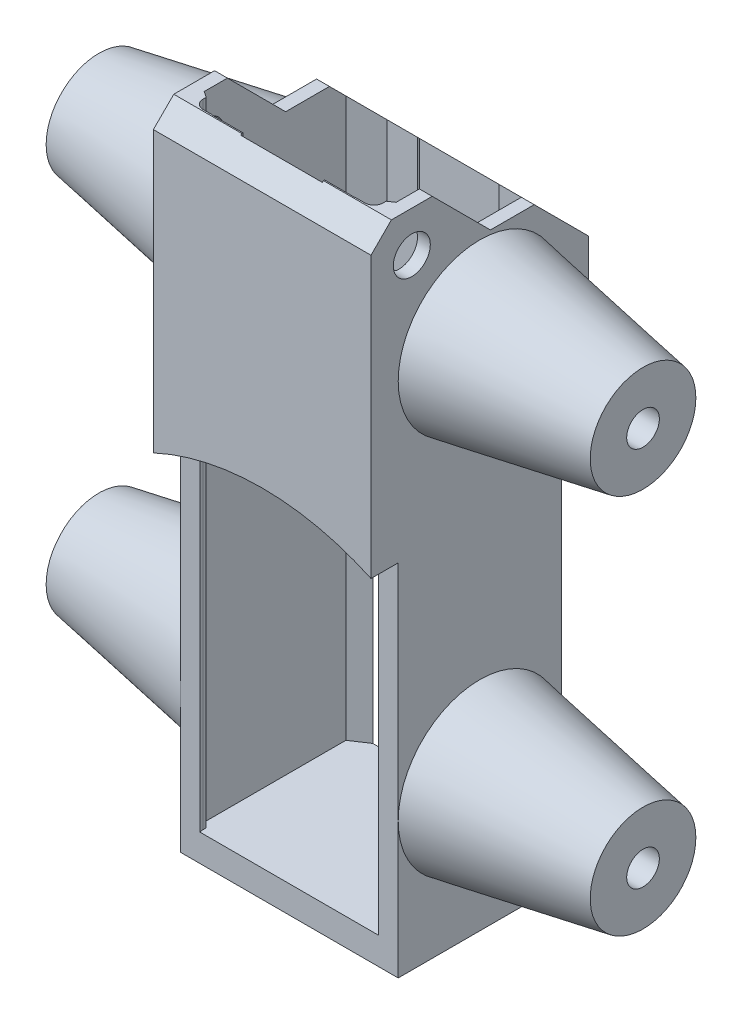
SolidWorks part; units mm, degrees
ref_plane "Front Plane" through (0, 0, 0) normal (0, 0, 1) x (1, 0, 0)
ref_plane "Top Plane" through (0, 0, 0) normal (0, 1, 0) x (1, 0, 0)
ref_plane "Right Plane" through (0, 0, 0) normal (1, 0, 0) x (0, 0, -1)
sketch "Sketch1" plane through (0, 0, 0) normal (0, 1, 0) x (1, 0, 0)
  line L0 (4.7625, -10.1854) -> (8.3298, -10.1854)
  line L5 (-4.7625, 10.1854) -> (-4.7625, 10.4394)
  line L6 (-12.7, -12.7) -> (12.7, -12.7)
  line L7 (4.7625, 10.1854) -> (8.3298, 10.1854)
  line L8 (-8.3298, 10.1854) -> (-11.2014, 8.271)
  line L9 (-8, 10.1) -> (-11, 8.1) construction
  line L10 (0, 0) -> (-11.2014, 0) construction
  line L11 (0, 0) -> (0, 10.4394) construction
  line L12 (-8.3298, -10.1854) -> (-8.3769, -10.154)
  line L13 (8.3298, -10.1854) -> (8.3769, -10.154)
  line L14 (8.3298, 10.1854) -> (11.2014, 8.271)
  line L15 (-8.3298, 10.1854) -> (-4.7625, 10.1854)
  line L16 (-12.7, 12.7) -> (-12.7, -12.7)
  line L17 (12.7, 12.7) -> (12.7, -12.7)
  line L34 (-10.504, -8.7359) -> (-11.2014, -8.271)
  line L35 (8.3769, -10.154) -> (9.4165, -10.154)
  line L36 (9.5863, -10.1409) -> (9.6154, -10.1409)
  line L37 (-9.5863, -10.1409) -> (-9.6154, -10.1409)
  line L38 (-8.75, -10.154) -> (-9.4165, -10.154)
  line L39 (-10.504, -9.1) -> (-10.504, -8.9)
  line L40 (-9.5863, -10.1409) -> (-9.6154, -10.1409)
  line L41 (-8.3769, -10.154) -> (-9.4165, -10.154)
  line L42 (-10.504, -9.1) -> (-10.504, -8.7359)
  line L43 (10.504, -9.1) -> (10.504, -8.7359)
  line L44 (10.504, -8.7359) -> (11.2014, -8.271)
  line L284 (-12.7, 12.7) -> (12.7, 12.7)
  line L286 (-12.7, -12.7) -> (12.7, 12.7) construction
  line L287 (-12.7, 12.7) -> (12.7, -12.7) construction
  line L288 (-8.3298, -10.1854) -> (-4.7625, -10.1854)
  line L289 (-11.2014, -8.271) -> (-11.2014, 8.271)
  line L291 (11.2014, -8.271) -> (11.2014, 8.271)
  line L326 (-4.7625, 10.4394) -> (4.7625, 10.4394)
  line L327 (4.7625, 10.4394) -> (4.7625, 10.1854)
  line L328 (-4.7625, -10.1854) -> (-4.7625, -10.4394)
  line L335 (-4.7625, -10.4394) -> (4.7625, -10.4394)
  line L338 (4.7625, -10.4394) -> (4.7625, -10.1854)
  arc A7 (9.5863, -10.1409) -> (9.4165, -10.154) centre (9.4168, -9.0458) cw
  arc A8 (-9.5863, -10.1409) -> (-9.4165, -10.154) centre (-9.4168, -9.0458) ccw
  arc A9 (-10.504, -9.1) -> (-9.6154, -10.1409) centre (-9.45, -9.1) ccw
  arc A10 (-9.5863, -10.1409) -> (-9.4165, -10.154) centre (-9.4168, -9.0458) ccw
  arc A11 (-10.504, -9.1) -> (-9.6154, -10.1409) centre (-9.45, -9.1) ccw
  arc A12 (10.504, -9.1) -> (9.6154, -10.1409) centre (9.45, -9.1) cw
  point P0 (0, 0)
  point P6 (0, 0)
  point P15 (0, 10.4394)
  point P23 (0, -10.4394)
  dimension "D1" = 25.4
  dimension "D2" = 25.4
  dimension "D3" = 0.254
  dimension "D5" = 9.525
  dimension "D6" = 22.4028
  dimension "D7" = 0.254
  dimension "D8" = 20.3708
  dimension "D9" = 0.254
  dimension "D15" = 0.254
extrude "Boss-Extrude1" add sketch "Sketch1" along normal blind 67.056
sketch "Sketch4" plane through (0, 0, 0) normal (0, -1, 0) x (-1, 0, 0)
  line L1 (12.7, -12.7) -> (-12.7, -12.7)
  line L2 (12.7, -12.7) -> (12.7, 12.7)
  line L3 (12.7, 12.7) -> (-12.7, 12.7)
  line L4 (-12.7, -12.7) -> (-12.7, 12.7)
extrude "Boss-Extrude4" add sketch "Sketch4" along normal blind 3.175
sketch "Sketch5" plane through (0, 0, -12.7) normal (0, 0, -1) x (-1, 0, 0)
  circle A0 centre (0, 11.43) radius 30.1625
  dimension "D2" = 60.325
  dimension "D1" = 11.43
extrude "Cut-Extrude1" cut sketch "Sketch5" against normal blind 3.175
mirror "Mirror1" about plane through (0, 0, 0) normal (0, 0, 1) of "Cut-Extrude1"
sketch "Sketch7" plane through (12.7, 0, 0) normal (1, 0, 0) x (0, 0, -1)
  circle A0 centre (0, 12.7) radius 9.525
  dimension "D2" = 19.05
  dimension "D1" = 12.7
extrude "Boss-Extrude6" add sketch "Sketch7" along normal blind 19.05 draft 10
sketch "Sketch8" plane through (31.75, 0, 0) normal (1, 0, 0) x (0, 0, -1)
  circle A0 centre (0, 12.7) radius 1.905
  dimension "D1" = 3.81
extrude "Cut-Extrude2" cut sketch "Sketch8" against normal blind 12.7
pattern_linear "LPattern1" count 2 spacing 44.45 along (0, 1, 0) of "Boss-Extrude6", "Cut-Extrude2"
mirror "Mirror2" about plane through (0, 0, 0) normal (1, 0, 0) of "LPattern1", "Boss-Extrude6", "Cut-Extrude2"
chamfer "Chamfer1" distance 6.35 angle 45 1 edges at (0, 67.056, -12.7)
sketch "Sketch9" plane through (12.7, 0, 0) normal (1, 0, 0) x (0, 0, -1)
  line L0 (-12.7, 67.056) -> (-12.7, 71.4692)
  line L1 (-12.7, 71.4692) -> (-10.3188, 73.8505)
  line L2 (-10.3188, 73.8505) -> (-5.5563, 73.8505)
  line L3 (-5.5563, 73.8505) -> (1.2383, 67.056)
  line L4 (-12.7, 67.056) -> (1.2383, 67.056)
  line L5 (-12.7, 67.056) -> (6.35, 67.056) construction
  line L6 (-12.7, 67.056) -> (-12.7, 38.7885) construction
  circle A0 centre (-7.9375, 69.088) radius 1.905
  point P7 (-7.9375, 73.8505)
  dimension "D1" = 3.81
  dimension "D2" = 45
  dimension "D3" = 4.7625
  dimension "D4" = 4.7625
  dimension "D5" = 4.7625
  dimension "D6" = 2.032
extrude "Boss-Extrude7" add sketch "Sketch9" against normal up to surface (25.4 mm away) up to face at (-12.7, 2.3812, 0)
sketch "Sketch11" plane through (0, 67.056, 0) normal (0, -1, 0) x (1, 0, 0)
  line L18 (11.2014, -1.2383) -> (11.2014, 8.271)
  line L19 (11.2014, 8.271) -> (10.504, 8.7359)
  line L20 (10.504, 8.7359) -> (10.504, 9.1)
  line L21 (9.6154, 10.1409) -> (9.5863, 10.1409)
  line L22 (9.4165, 10.154) -> (8.3769, 10.154)
  line L23 (8.3769, 10.154) -> (8.3298, 10.1854)
  line L24 (8.3298, 10.1854) -> (4.7625, 10.1854)
  line L25 (4.7625, 10.1854) -> (4.7625, 10.4394)
  line L26 (4.7625, 10.4394) -> (-4.7625, 10.4394)
  line L27 (-4.7625, 10.4394) -> (-4.7625, 10.1854)
  line L28 (-4.7625, 10.1854) -> (-8.3298, 10.1854)
  line L29 (-8.3298, 10.1854) -> (-8.3769, 10.154)
  line L30 (-8.3769, 10.154) -> (-9.4165, 10.154)
  line L31 (-9.5863, 10.1409) -> (-9.6154, 10.1409)
  line L32 (-10.504, 9.1) -> (-10.504, 8.7359)
  line L33 (-10.504, 8.7359) -> (-11.2014, 8.271)
  line L34 (-11.2014, 8.271) -> (-11.2014, -1.2383)
  line L35 (-11.2014, -1.2383) -> (11.2014, -1.2383)
  line L36 (11.2014, -1.2383) -> (11.2014, 8.271)
  line L37 (11.2014, 8.271) -> (10.504, 8.7359)
  line L38 (10.504, 8.7359) -> (10.504, 9.1)
  line L39 (9.6154, 10.1409) -> (9.5863, 10.1409)
  line L40 (9.4165, 10.154) -> (8.3769, 10.154)
  line L41 (8.3769, 10.154) -> (8.3298, 10.1854)
  line L42 (8.3298, 10.1854) -> (4.7625, 10.1854)
  line L43 (4.7625, 10.1854) -> (4.7625, 10.4394)
  line L44 (4.7625, 10.4394) -> (-4.7625, 10.4394)
  line L45 (-4.7625, 10.4394) -> (-4.7625, 10.1854)
  line L46 (-4.7625, 10.1854) -> (-8.3298, 10.1854)
  line L47 (-8.3298, 10.1854) -> (-8.3769, 10.154)
  line L48 (-8.3769, 10.154) -> (-9.4165, 10.154)
  line L49 (-9.5863, 10.1409) -> (-9.6154, 10.1409)
  line L50 (-10.504, 9.1) -> (-10.504, 8.7359)
  line L51 (-10.504, 8.7359) -> (-11.2014, 8.271)
  line L52 (-11.2014, 8.271) -> (-11.2014, -1.2383)
  line L53 (-11.2014, -1.2383) -> (11.2014, -1.2383)
  arc A4 (10.504, 9.1) -> (9.6154, 10.1409) centre (9.45, 9.1) ccw
  arc A5 (9.5863, 10.1409) -> (9.4165, 10.154) centre (9.4168, 9.0458) ccw
  arc A6 (-9.4165, 10.154) -> (-9.5863, 10.1409) centre (-9.4168, 9.0458) ccw
  arc A7 (-9.6154, 10.1409) -> (-10.504, 9.1) centre (-9.45, 9.1) ccw
  arc A8 (10.504, 9.1) -> (9.6154, 10.1409) centre (9.45, 9.1) ccw
  arc A9 (9.5863, 10.1409) -> (9.4165, 10.154) centre (9.4168, 9.0458) ccw
  arc A10 (-9.4165, 10.154) -> (-9.5863, 10.1409) centre (-9.4168, 9.0458) ccw
  arc A11 (-9.6154, 10.1409) -> (-10.504, 9.1) centre (-9.45, 9.1) ccw
  dimension "D1" = 0
extrude "Cut-Extrude3" cut sketch "Sketch11" against normal through all
sketch "Sketch12" plane through (12.7, 0, 0) normal (1, 0, 0) x (0, 0, -1)
  circle A0 centre (-7.9375, 69.088) radius 2.159
  dimension "D1" = 4.318
extrude "Cut-Extrude4" cut sketch "Sketch12" against normal up to next
